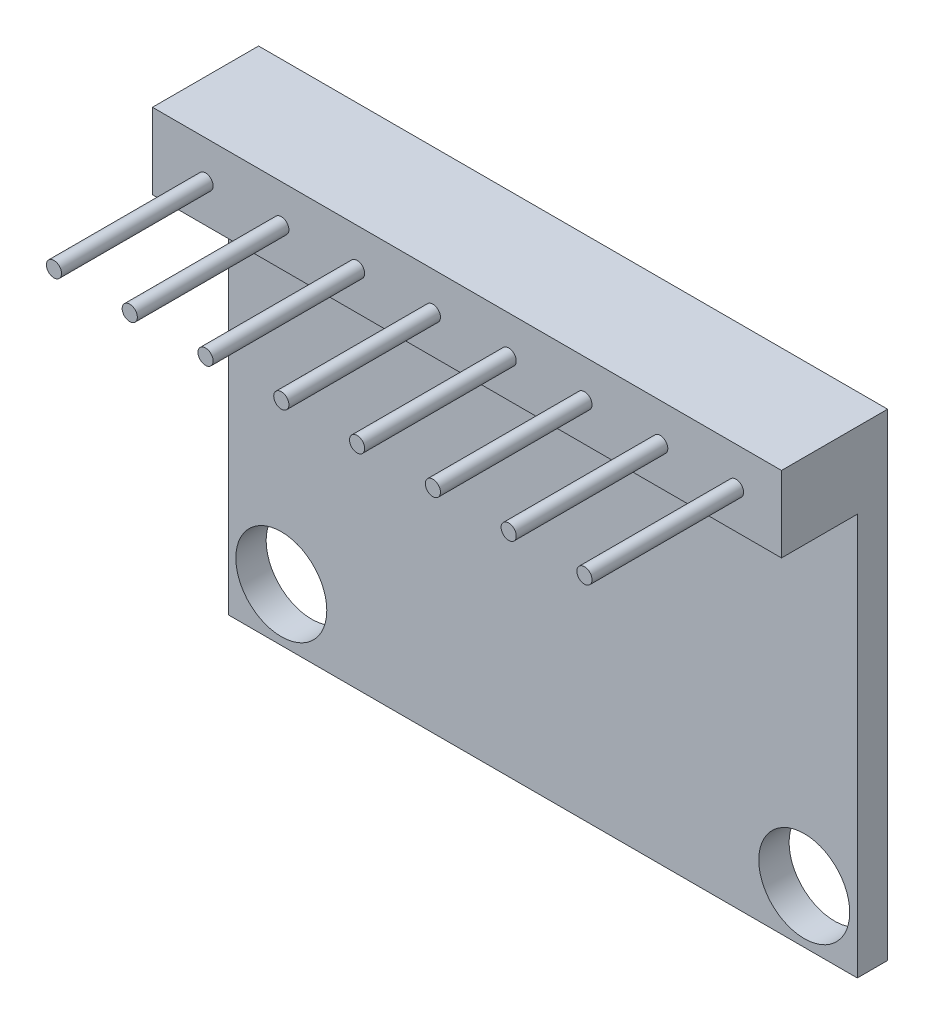
SolidWorks part; units mm, degrees
ref_plane "Plan de face" through (0, 0, 0) normal (0, 0, 1) x (1, 0, 0)
ref_plane "Plan de dessus" through (0, 0, 0) normal (0, 1, 0) x (1, 0, 0)
ref_plane "Plan de droite" through (0, 0, 0) normal (1, 0, 0) x (0, 0, -1)
sketch "Esquisse1" plane through (0, 0, 0) normal (0, 0, 1) x (1, 0, 0)
  line L1 (0, 0) -> (-20.75, 0)
  line L2 (0, 0) -> (0, 15.75)
  line L3 (0, 15.75) -> (-20.75, 15.75)
  line L4 (-20.75, 0) -> (-20.75, 15.75)
  dimension "D1" = 20.75
  dimension "D2" = 15.75
extrude "Boss.-Extru.1" add sketch "Esquisse1" along normal blind 1
sketch "Esquisse2" plane through (0, 0, 1) normal (0, 0, 1) x (1, 0, 0)
  line L0 (0, 0) -> (0, 15.75) construction
  line L1 (-20.75, 15.75) -> (0, 15.75)
  line L2 (-20.75, 15.75) -> (-20.75, 13.25)
  line L3 (-20.75, 13.25) -> (0, 13.25)
  line L4 (0, 15.75) -> (0, 13.25)
  dimension "D1" = 2.5
extrude "Boss.-Extru.2" add sketch "Esquisse2" along normal blind 2.5
sketch "Esquisse3" plane through (0, 0, 3.5) normal (0, 0, 1) x (1, 0, 0)
  line L0 (-20.75, 14.5) -> (-19, 14.5) construction
  line L1 (-20.75, 15.75) -> (-20.75, 13.25) construction
  line L2 (-19, 14.5) -> (-1.4318, 14.5) construction
  line L3 (-1.4318, 14.5) -> (0, 14.5) construction
  line L4 (0, 13.25) -> (0, 15.75) construction
  circle A0 centre (-19, 14.5) radius 0.25
  circle A1 centre (-16.5, 14.5) radius 0.25
  circle A2 centre (-14, 14.5) radius 0.25
  circle A3 centre (-11.5, 14.5) radius 0.25
  circle A4 centre (-9, 14.5) radius 0.25
  circle A5 centre (-6.5, 14.5) radius 0.25
  circle A6 centre (-4, 14.5) radius 0.25
  circle A7 centre (-1.5, 14.5) radius 0.25
  dimension "D2" = 0.5
  dimension "D1" = 1.75
  dimension "D3" = 8
extrude "Boss.-Extru.3" add sketch "Esquisse3" along normal blind 5 and the other way blind 4
sketch "Esquisse4" plane through (0, 0, 0) normal (0, 0, -1) x (-1, 0, 0)
  line L0 (0, 7.875) -> (20.75, 7.875) construction
  line L1 (0, 0) -> (0, 15.75) construction
  line L2 (20.75, 15.75) -> (20.75, 0) construction
  line L3 (8.375, 7.875) -> (12.375, 7.875) construction
  line L4 (4.375, 9.875) -> (4.875, 9.875)
  line L5 (4.375, 9.875) -> (4.375, 7.875)
  line L6 (4.375, 7.875) -> (4.875, 7.875)
  line L7 (4.875, 9.875) -> (4.875, 7.875)
  line L8 (5.375, 9.875) -> (5.875, 9.875)
  line L9 (5.375, 9.875) -> (5.375, 8.875)
  line L10 (5.375, 8.875) -> (5.875, 8.875)
  line L11 (5.875, 9.875) -> (5.875, 8.875)
  line L12 (6.375, 9.875) -> (6.875, 9.875)
  line L13 (6.375, 9.875) -> (6.375, 7.875)
  line L14 (6.375, 7.875) -> (6.875, 7.875)
  line L15 (6.875, 9.875) -> (6.875, 7.875)
  line L16 (13.875, 9.875) -> (14.375, 9.875)
  line L17 (13.875, 9.875) -> (13.875, 7.875)
  line L18 (13.875, 7.875) -> (14.375, 7.875)
  line L19 (14.375, 9.875) -> (14.375, 7.875)
  line L20 (14.875, 9.875) -> (15.375, 9.875)
  line L21 (14.875, 9.875) -> (14.875, 8.875)
  line L22 (14.875, 8.875) -> (15.375, 8.875)
  line L23 (15.375, 9.875) -> (15.375, 8.875)
  line L24 (15.875, 9.875) -> (16.375, 9.875)
  line L25 (15.875, 9.875) -> (15.875, 7.875)
  line L26 (15.875, 7.875) -> (16.375, 7.875)
  line L27 (16.375, 9.875) -> (16.375, 7.875)
  line L28 (8.375, 9.875) -> (12.375, 9.875)
  line L29 (8.375, 9.875) -> (8.375, 5.875)
  line L30 (8.375, 5.875) -> (12.375, 5.875)
  line L31 (12.375, 9.875) -> (12.375, 5.875)
  line L32 (4.375, 6.875) -> (4.875, 6.875)
  line L33 (4.375, 6.875) -> (4.375, 5.875)
  line L34 (4.375, 5.875) -> (4.875, 5.875)
  line L35 (4.875, 6.875) -> (4.875, 5.875)
  line L36 (6.375, 6.875) -> (6.875, 6.875)
  line L37 (6.375, 6.875) -> (6.375, 4.875)
  line L38 (6.375, 4.875) -> (6.875, 4.875)
  line L39 (6.875, 6.875) -> (6.875, 4.875)
  line L40 (8.7567, 4.0741) -> (11.2567, 4.0741)
  line L41 (8.7567, 4.0741) -> (8.7567, 3.0741)
  line L42 (8.7567, 3.0741) -> (11.2567, 3.0741)
  line L43 (11.2567, 4.0741) -> (11.2567, 3.0741)
  line L44 (13.875, 6.875) -> (14.375, 6.875)
  line L45 (13.875, 6.875) -> (13.875, 5.875)
  line L46 (13.875, 5.875) -> (14.375, 5.875)
  line L47 (14.375, 6.875) -> (14.375, 5.875)
  line L48 (15.875, 6.875) -> (16.375, 6.875)
  line L49 (15.875, 6.875) -> (15.875, 4.875)
  line L50 (15.875, 4.875) -> (16.375, 4.875)
  line L51 (16.375, 6.875) -> (16.375, 4.875)
  line L52 (2, 2) -> (2, 0) construction
  line L53 (20.75, 0) -> (0, 0) construction
  line L54 (2, 2) -> (0, 2) construction
  line L55 (18.75, 2) -> (20.75, 2) construction
  line L56 (18.75, 2) -> (18.75, 0) construction
  circle A0 centre (2, 2) radius 1.5
  circle A1 centre (18.75, 2) radius 1.5
  point P60 (10.375, 7.875)
  point P61 (10.375, 7.875)
  point P62 (10.375, 7.9577)
  point P63 (10.375, 7.9577)
  dimension "D45" = 3
  dimension "D46" = 3
  dimension "D1" = 0.5
  dimension "D2" = 0.5
  dimension "D3" = 0.5
  dimension "D4" = 0.5
  dimension "D5" = 0.5
  dimension "D6" = 0.5
  dimension "D7" = 0.5
  dimension "D8" = 0.5
  dimension "D9" = 0.5
  dimension "D10" = 0.5
  dimension "D11" = 1.5
  dimension "D12" = 1.5
  dimension "D13" = 4
  dimension "D14" = 4
  dimension "D15" = 0
  dimension "D16" = 0
  dimension "D17" = 0
  dimension "D18" = 0
  dimension "D19" = 2
  dimension "D20" = 1
  dimension "D21" = 2
  dimension "D22" = 2
  dimension "D23" = 1
  dimension "D24" = 2
  dimension "D25" = 0
  dimension "D26" = 0
  dimension "D27" = 0
  dimension "D28" = 0
  dimension "D29" = 0.5
  dimension "D30" = 2
  dimension "D31" = 1
  dimension "D32" = 0.5
  dimension "D33" = 0.5
  dimension "D34" = 0.5
  dimension "D35" = 0
  dimension "D36" = 0
  dimension "D37" = 1
  dimension "D38" = 2
  dimension "D39" = 1
  dimension "D40" = 1
  dimension "D41" = 1
  dimension "D42" = 1
  dimension "D43" = 2.5
  dimension "D44" = 1
  dimension "D47" = 2
  dimension "D48" = 2
  dimension "D49" = 2
  dimension "D50" = 2
extrude "Boss.-Extru.4" add sketch "Esquisse4" along normal blind 0.5 contours L15 L12 L13 L14 | L11 L8 L9 L10 | L7 L4 L5 L6 | L35 L32 L33 L34 | L39 L36 L37 L38 | L43 L40 L41 L42 | L29 L28 L31 L30 | L17 L16 L19 L18 | L25 L24 L27 L26 | L21 L20 L23 L22 | L45 L44 L47 L46 | L49 L48 L51 L50 region at (-4.625, 8.875, 0) region at (-5.625, 9.375, 0) region at (-6.625, 8.875, 0) region at (-4.625, 6.375, 0) region at (-6.625, 5.875, 0) region at (-10.0067, 3.5741, 0)
sketch "Esquisse5" plane through (0, 0, 0) normal (0, 0, -1) x (-1, 0, 0)
  line L0 (0, 3.5) -> (20.75, 3.5) construction
  line L1 (0, 0) -> (0, 15.75) construction
  line L2 (20.75, 15.75) -> (20.75, 0) construction
  line L3 (20.75, 3.5) -> (20.75, 0) construction
  line L4 (20.75, 0) -> (0, 0) construction
  line L5 (20.75, 0) -> (17.25, 0) construction
  line L6 (17.25, 0) -> (3.5, 0) construction
  line L7 (3.5, 0) -> (0, 0) construction
  line L8 (0, 0) -> (0, 3.5) construction
  line L9 (17.25, 0) -> (20.75, 3.5) construction
  line L10 (0, 3.5) -> (3.5, 0) construction
  circle A0 centre (1.75, 1.75) radius 1.5
  circle A1 centre (19, 1.75) radius 1.5
  dimension "D4" = 3
  dimension "D5" = 3
  dimension "D1" = 3.5
  dimension "D2" = 3.5
  dimension "D3" = 3.5
extrude "Enlèv. mat.-Extru.1" cut sketch "Esquisse5" against normal blind 5
sketch "Esquisse6" plane through (0, 0, 0) normal (0, 0, -1) x (-1, 0, 0)
  line L0 (15.875, 9.875) -> (16.375, 9.875) construction
  line L1 (17.75, 9.875) -> (20.25, 9.875)
  line L2 (17.75, 9.875) -> (17.75, 7.875)
  line L3 (17.75, 7.875) -> (20.25, 7.875)
  line L4 (20.25, 9.875) -> (20.25, 7.875)
  line L5 (20.75, 15.75) -> (20.75, 0) construction
  dimension "D1" = 2.5
  dimension "D2" = 2
  dimension "D3" = 0
  dimension "D4" = 0.5
extrude "Boss.-Extru.5" add sketch "Esquisse6" along normal blind 0.5
